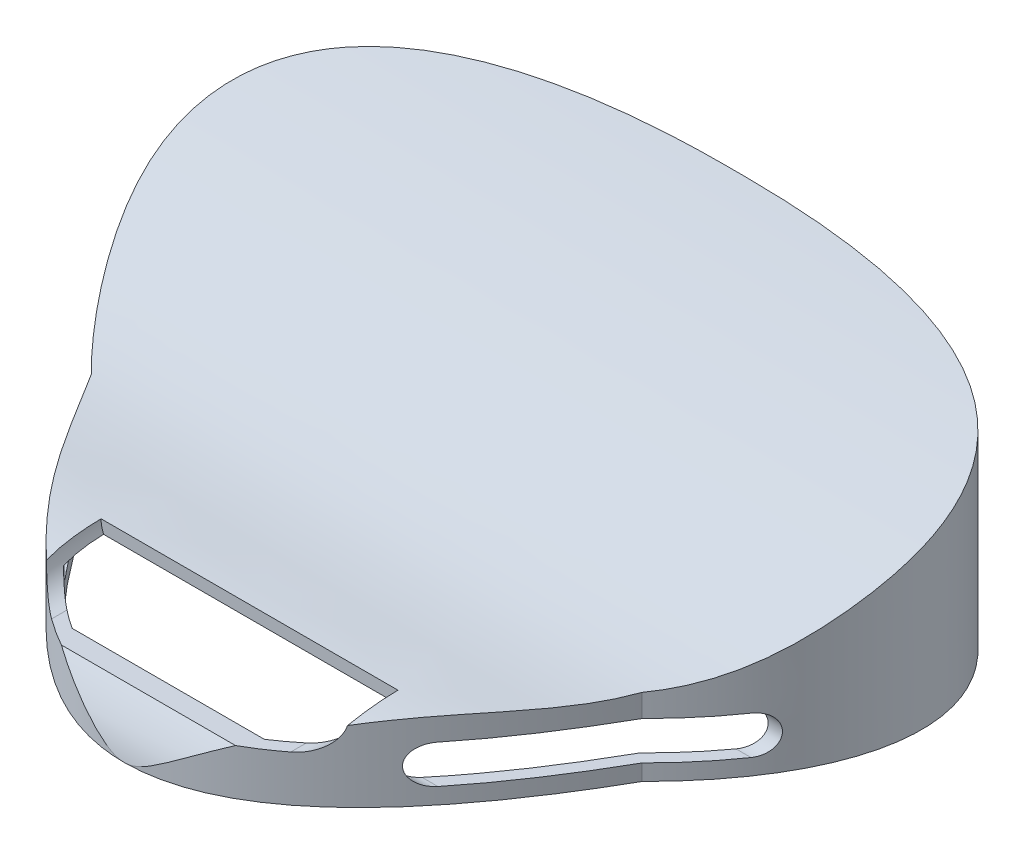
SolidWorks part; units mm, degrees
ref_plane "Front Plane" through (0, 0, 0) normal (0, 0, 1) x (1, 0, 0)
ref_plane "Top Plane" through (0, 0, 0) normal (0, 1, 0) x (1, 0, 0)
ref_plane "Right Plane" through (0, 0, 0) normal (1, 0, 0) x (0, 0, -1)
sketch "Sketch1" plane through (0, 0, 0) normal (0, 1, 0) x (1, 0, 0)
  line L0 (-50.7636, 0) -> (39.2364, 0) construction
  line L1 (39.2364, -39.6176) -> (-50.7636, -39.6176) construction
  line L2 (-50.7636, 0) -> (-50.7636, -39.6176) construction
  line L3 (39.2364, 0) -> (39.2364, -39.6176) construction
  line L4 (-5.7636, -39.6176) -> (-5.7636, 60) construction
  line L5 (-76.4362, 60) -> (59.5851, 60) construction
  line L7 (-7.3923, 60.0049) -> (-7.3923, 0) construction
  line L9 (-27.6876, 0) -> (-27.6876, -39.6176) construction
  line L21 (-50.7636, -15.2373) -> (39.2364, -15.2373) construction
  spline S0 degree 2 poles (-50.7636, 0) (-5.7636, -79.2352) (39.2364, 0) knots 0 0 0 1 1 1
  spline S1 degree 3 poles (-50.7636, 0) (-76.9258, 26.0498) (-74.9674, 60.482) (-5.7636, 60) knots 0 0 0 0 1 1 1 1
  spline S2 degree 3 poles (39.2364, 0) (65.3987, 26.0498) (63.4403, 60.482) (-5.7636, 60) knots 0 0 0 0 1 1 1 1
extrude "Boss-Extrude1" add sketch "Sketch1" along normal blind 34
ref_plane "Plane1" through (100, 0, 0) normal (1, 0, 0) x (0, 0, -1)
sketch "Sketch4" plane through (100, 0, 0) normal (1, 0, 0) x (0, 0, -1)
  line L0 (60.005, 34) -> (60.005, 0) construction
  line L1 (60.005, 0) -> (60.005, 34) construction
  line L2 (60.005, 0) -> (-39.6176, 0) construction
  line L3 (-39.6176, 0) -> (-39.6176, 34) construction
  line L4 (-39.6176, 34) -> (-39.6176, 0) construction
  line L5 (0, 34) -> (-39.6176, 34) construction
  line L6 (-39.6176, 34) -> (60.005, 34) construction
  line L8 (-39.6176, 34) -> (-39.6176, 0)
  line L9 (-39.6176, 34) -> (60.005, 34)
  spline S0 degree 3 poles (60.005, 34) (46.2153, 31.8238) (26.1833, 25.4472) (1.3008, 10.1129) (-23.6745, 14.5365) (-37.8836, 9.1703) (-39.6176, 0) knots 0 0 0 0 0.367689 0.568576 0.750394 1 1 1 1
extrude "Cut-Extrude3" cut sketch "Sketch4" against normal through all
shell "Shell2" thickness 2 removed face at (-5.7636, 0, -5.0956)
ref_plane "Plane2" through (0, 0, 39.6176) normal (0, 0, 1) x (1, 0, 0)
sketch "Sketch10" plane through (0, 0, 39.6176) normal (0, 0, 1) x (1, 0, 0)
  line L0 (-24.4764, 12.5987) -> (13.8896, 12.5987) construction
  line L1 (26.8163, 12.5987) -> (-38.3434, 12.5987) construction
  line L2 (-24.4764, 17.6659) -> (13.8896, 17.6659)
  line L3 (-24.4764, 7.5314) -> (13.8896, 7.5314)
  arc A0 (-24.4764, 17.6659) -> (-24.4764, 7.5314) centre (-24.4764, 12.5987) ccw
  arc A1 (13.8896, 7.5314) -> (13.8896, 17.6659) centre (13.8896, 12.5987) ccw
  point P4 (-5.2934, 12.5987)
extrude "Cut-Extrude5" cut sketch "Sketch10" against normal blind 20
sketch "Sketch11" plane through (100, 0, 0) normal (1, 0, 0) x (0, 0, -1)
  line L0 (-20.0186, 5.7657) -> (9.6574, 5.7657) construction
  line L1 (-20.0186, 8.9032) -> (9.6574, 8.9032)
  line L2 (-20.0186, 2.6281) -> (9.6574, 2.6281)
  arc A0 (-20.0186, 8.9032) -> (-20.0186, 2.6281) centre (-20.0186, 5.7657) ccw
  arc A1 (9.6574, 2.6281) -> (9.6574, 8.9032) centre (9.6574, 5.7657) ccw
  point P2 (-5.1806, 5.7657)
extrude "Cut-Extrude6" cut sketch "Sketch11" against normal through all
